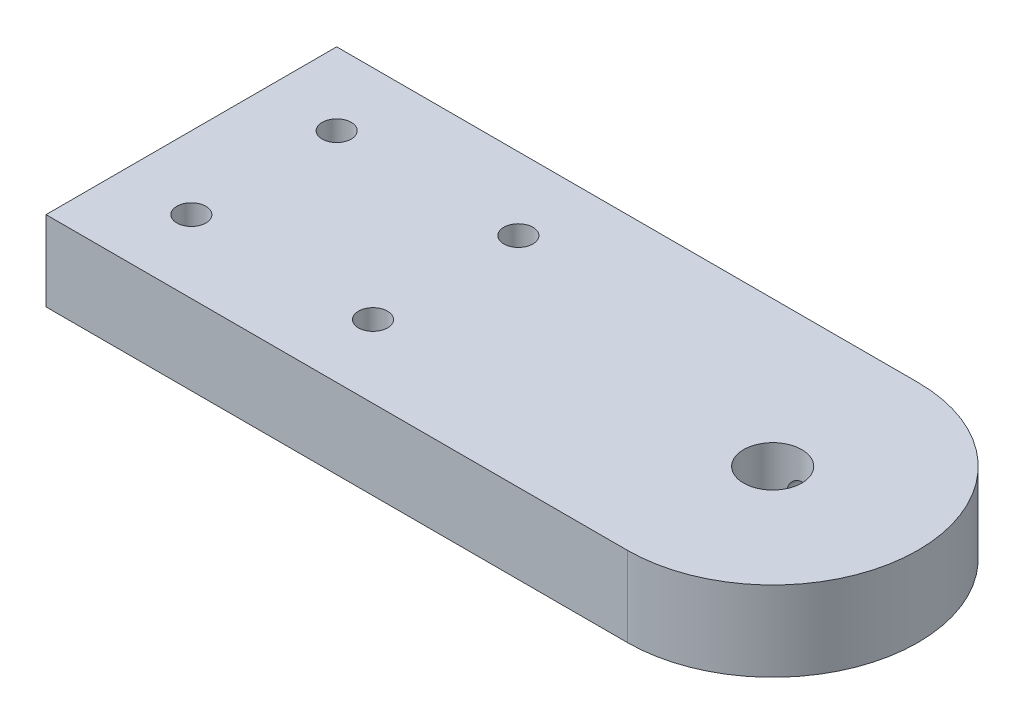
SolidWorks part; units mm, degrees
material "1060 Alloy"
ref_plane "Front Plane" through (0, 0, 0) normal (0, 0, 1) x (1, 0, 0)
ref_plane "Top Plane" through (0, 0, 0) normal (0, 1, 0) x (1, 0, 0)
ref_plane "Right Plane" through (0, 0, 0) normal (1, 0, 0) x (0, 0, -1)
sketch "Sketch1" plane through (0, 0, 0) normal (0, 1, 0) x (1, 0, 0)
  line L0 (-80, 20) -> (20, 20)
  line L1 (20, 20) -> (20, -5)
  line L2 (20, -5) -> (-80, -5) construction
  line L3 (-80, -5) -> (-80, 20)
  line L4 (20, -5) -> (20, -20)
  line L5 (20, -20) -> (-80, -20)
  line L6 (-80, -20) -> (-80, -5)
  line L7 (20, -10) -> (-70, -10) construction
  line L8 (-70, -10) -> (-70, -5) construction
  line L9 (-70, -5) -> (-70, 10) construction
  line L10 (-70, 10) -> (20, 10) construction
  circle A0 centre (0, 0) radius 4
  circle A1 centre (-70, 10) radius 2
  circle A2 centre (-45, 10) radius 2
  circle A3 centre (-45, -10) radius 2
  circle A4 centre (-70, -10) radius 2
  arc A5 (0, -20) -> (0, 20) centre (0, 0) ccw
  point P2 (0, 1.5652)
  dimension "D1" = 8
  dimension "D7" = 4
  dimension "D2" = 20
  dimension "D3" = 25
  dimension "D4" = 20
  dimension "D5" = 15
  dimension "D6" = 100
  dimension "D9" = 25
  dimension "D8" = 10
extrude "Boss-Extrude1" add sketch "Sketch1" along normal blind 11 contours L5 A5 L0 L3 L6 A4 A3 A2 A1 A0 region at (-32.1307, 0, 0)
hole_wizard "M4 Tapped Hole1" positions "Sketch2" profile "Sketch3" tap size "M4" standard "ISO"
sketch "Sketch2" plane through (0, 0, -20) normal (0, 0, -1) x (-1, 0, 0)
  line L0 (0, 6.05) -> (0, -6.05) construction
  line L1 (0, 11) -> (0, 0) construction
  point P0 (0, 5.5)
  point P11 (0, 5.5)
sketch "Sketch3" plane through (0, 5.5, -20) normal (1, 0, 0) x (0, 1, 0)
  line L0 (0, 0) -> (0, 20.9914)
  line L1 (0, 20.9914) -> (1.65, 20)
  line L2 (1.65, 20) -> (1.65, 0)
  line L5 (1.65, 0) -> (0, 0)
  line L10 (0, 20.9914) -> (-1.65, 20) construction
  line L11 (0, -6.35) -> (0, 107.95) construction
  dimension "Tap Drill Dia." = 3.3
  dimension "Tap Drill Depth" = 20
  dimension "Drill Angle" = 118
cosmetic thread "Hole Thread1" parameters "D1"=8, "D2"=4
